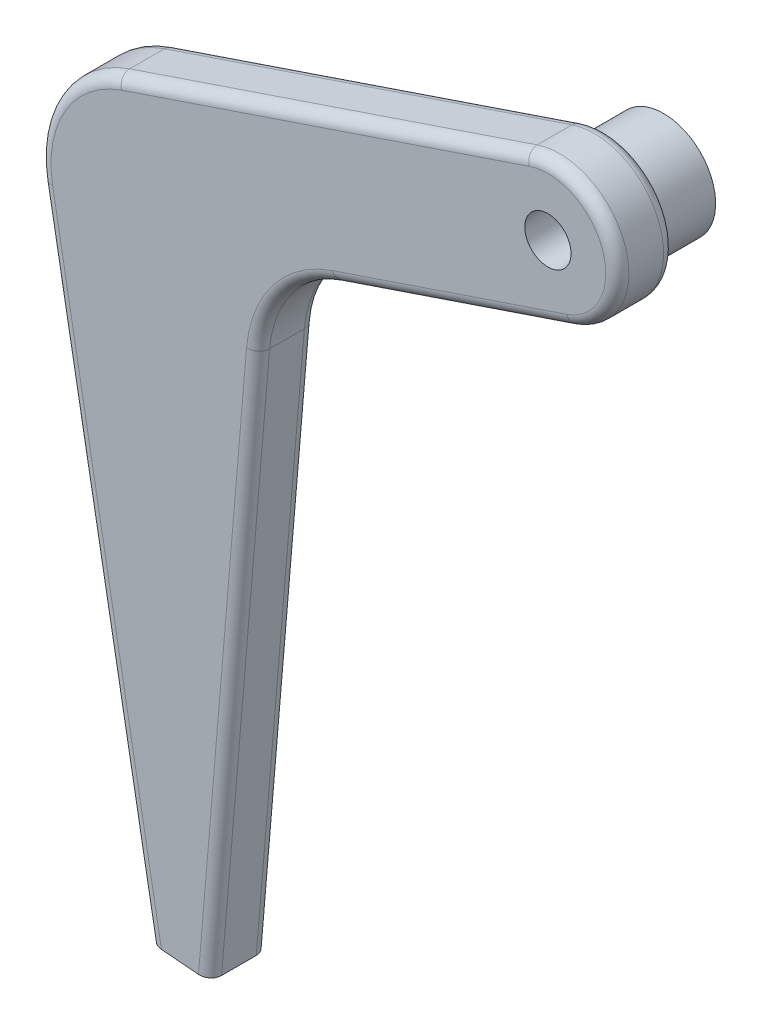
SolidWorks part; units mm, degrees
ref_plane "Front Plane" through (0, 0, 0) normal (0, 0, 1) x (1, 0, 0)
ref_plane "Top Plane" through (0, 0, 0) normal (0, 1, 0) x (1, 0, 0)
ref_plane "Right Plane" through (0, 0, 0) normal (1, 0, 0) x (0, 0, -1)
sketch "Sketch1" plane through (0, 0, 0) normal (0, 0, 1) x (1, 0, 0)
  line L0 (-10, -50) -> (-26.1505, -130.7992) construction
  line L2 (-8.0767, -55.6834) -> (-28.3007, -62.5274)
  line L3 (-47.1637, -56.2424) -> (-11.9233, -44.3166)
  line L4 (-44.4467, -119.7167) -> (-53.8015, -67.4774)
  line L5 (-39.2152, -120.1603) -> (-44.4467, -119.7167)
  line L6 (-35.0594, -71.1547) -> (-39.2152, -120.1603)
  circle A1 centre (-10, -50) radius 2
  arc A2 (-35.0594, -71.1547) -> (-28.3007, -62.5274) centre (-25.0952, -71.9997) cw
  arc A9 (-11.9233, -44.3166) -> (-8.0767, -55.6834) centre (-10, -50) cw
  arc A10 (-53.8015, -67.4774) -> (-47.1637, -56.2424) centre (-43.9581, -65.7147) cw
extrude "Boss-Extrude1" add sketch "Sketch1" along normal mid plane 5
fillet "Fillet1" radius 1 14 edges at (-37.1373, -95.6575, -2.5) (-32.9672, -65.8328, -2.5) (-49.1241, -93.597, -2.5) (-52.5677, -60.6279, -2.5) (-29.5435, -50.2795, -2.5) (-4.3166, -48.0767, -2.5) (-37.1373, -95.6575, 2.5) (-32.9672, -65.8328, 2.5) (-49.1241, -93.597, 2.5) (-52.5677, -60.6279, 2.5) (-29.5435, -50.2795, 2.5) (-4.3166, -48.0767, 2.5) (-18.1887, -59.1054, -2.5) (-18.1887, -59.1054, 2.5)
sketch "Sketch3" plane through (0, 0, -2.5) normal (0, 0, -1) x (-1, 0, 0)
  circle A0 centre (10, -50) radius 4.5
extrude "Boss-Extrude2" add sketch "Sketch3" along normal blind 5
sketch "Sketch4" plane through (0, 0, -7.5) normal (0, 0, -1) x (-1, 0, 0)
  circle A2 centre (10, -50) radius 2.5
extrude "Cut-Extrude1" cut sketch "Sketch4" against normal blind 3
sketch "Sketch5" plane through (0, 0, -2.5) normal (0, 0, 1) x (1, 0, 0)
  circle A2 centre (-10, -50) radius 1.1
extrude "Cut-Extrude2" cut sketch "Sketch5" against normal blind 3
